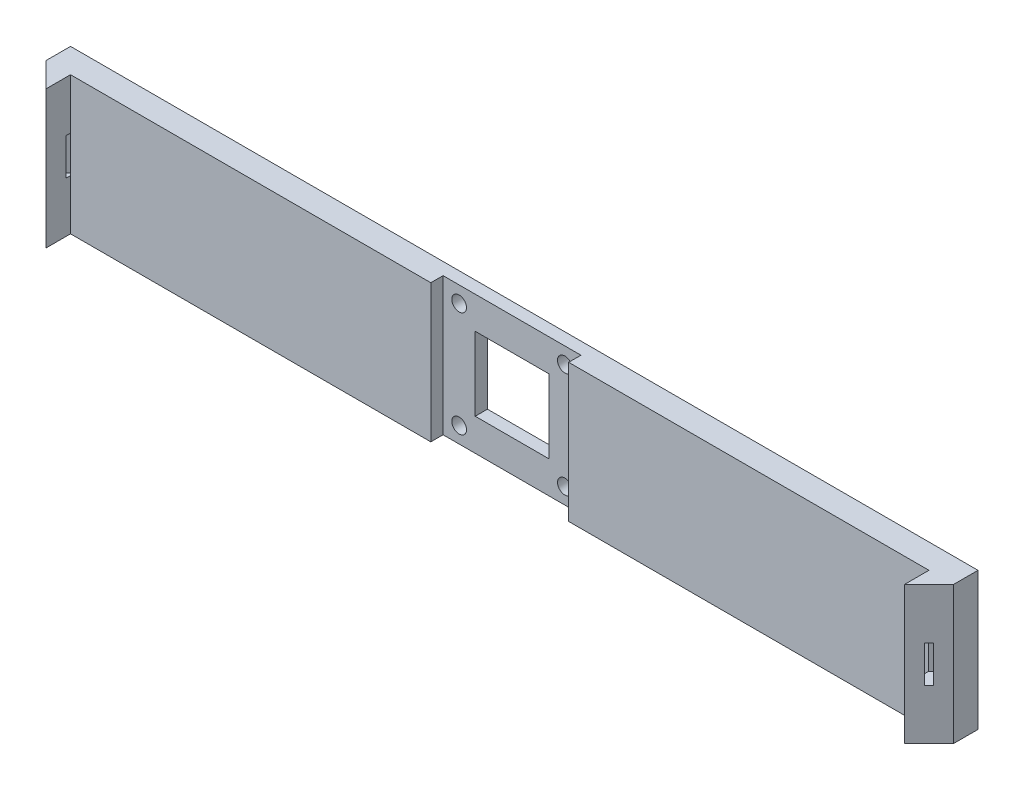
SolidWorks part; units mm, degrees
ref_plane "Front Plane" through (0, 0, 0) normal (0, 0, 1) x (1, 0, 0)
ref_plane "Top Plane" through (0, 0, 0) normal (0, 1, 0) x (1, 0, 0)
ref_plane "Right Plane" through (0, 0, 0) normal (1, 0, 0) x (0, 0, -1)
sketch "Sketch1" plane through (0, 0, 0) normal (0, 0, 1) x (1, 0, 0)
  line L1 (-175, -28.1) -> (175, -28.1)
  line L2 (-175, -28.1) -> (-175, 28.1)
  line L3 (-175, 28.1) -> (175, 28.1)
  line L4 (175, -28.1) -> (175, 28.1)
  line L5 (-175, -28.1) -> (175, 28.1) construction
  line L6 (-175, 28.1) -> (175, -28.1) construction
  point P0 (0, 0)
extrude "Boss-Extrude1" add sketch "Sketch1" along normal blind 10
sketch "Sketch2" plane through (0, 0, 10) normal (0, 0, 1) x (1, 0, 0)
  line L2 (175, 28.1) -> (-175, 28.1) construction
  line L3 (-28.1, -28.1) -> (28.1, -28.1)
  line L4 (-28.1, -28.1) -> (-28.1, 28.1)
  line L5 (-28.1, 28.1) -> (28.1, 28.1)
  line L6 (28.1, -28.1) -> (28.1, 28.1)
  point P8 (0, 0)
extrude "Cut-Extrude1" cut sketch "Sketch2" against normal blind 5
sketch "Sketch3" plane through (175, 0, 0) normal (1, 0, 0) x (0, 0, -1)
  line L1 (-10, 28.1) -> (0, 28.1)
  line L2 (-10, 28.1) -> (-10, -28.1)
  line L3 (-10, -28.1) -> (0, -28.1)
  line L4 (0, 28.1) -> (0, -28.1)
extrude "Boss-Extrude2" add sketch "Sketch3" along normal blind 10
sketch "Sketch4" plane through (0, 0, 10) normal (0, 0, 1) x (1, 0, 0)
  line L0 (28.1, -28.1) -> (185, -28.1) construction
  line L1 (185, 28.1) -> (175, 28.1)
  line L2 (185, 28.1) -> (185, -28.1)
  line L3 (185, -28.1) -> (175, -28.1)
  line L4 (175, 28.1) -> (175, -28.1)
extrude "Boss-Extrude3" add sketch "Sketch4" along normal blind 10
sketch "Sketch5" plane through (0, 28.1, 0) normal (0, 1, 0) x (1, 0, 0)
  line L0 (175, -20) -> (185, -10)
  line L1 (185, 0) -> (185, -20) construction
  line L2 (185, -10) -> (185, -20)
  line L3 (185, -20) -> (175, -20)
extrude "Cut-Extrude2" cut sketch "Sketch5" against normal blind 56.2
sketch "Sketch6" plane through (-175, 0, 0) normal (-1, 0, 0) x (0, 0, 1)
  line L1 (0, -28.1) -> (10, -28.1)
  line L2 (0, -28.1) -> (0, 28.1)
  line L3 (0, 28.1) -> (10, 28.1)
  line L4 (10, -28.1) -> (10, 28.1)
extrude "Boss-Extrude4" add sketch "Sketch6" along normal blind 10
sketch "Sketch7" plane through (0, 0, 10) normal (0, 0, 1) x (1, 0, 0)
  line L0 (-28.1, 28.1) -> (-185, 28.1) construction
  line L1 (-185, -28.1) -> (-175, -28.1)
  line L2 (-185, -28.1) -> (-185, 28.1)
  line L3 (-185, 28.1) -> (-175, 28.1)
  line L4 (-175, -28.1) -> (-175, 28.1)
extrude "Boss-Extrude5" add sketch "Sketch7" along normal blind 10
sketch "Sketch8" plane through (0, 28.1, 0) normal (0, 1, 0) x (1, 0, 0)
  line L0 (-175, -20) -> (-185, -10)
  line L1 (-185, -20) -> (-185, 0) construction
  line L2 (-185, -10) -> (-185, -20)
  line L3 (-185, -20) -> (-175, -20)
extrude "Cut-Extrude3" cut sketch "Sketch8" against normal blind 56.2
sketch "Sketch9" plane through (0, 0, 5) normal (0, 0, 1) x (1, 0, 0)
  line L3 (-15, -15) -> (15, -15)
  line L4 (-15, -15) -> (-15, 15)
  line L5 (-15, 15) -> (15, 15)
  line L6 (15, -15) -> (15, 15)
  point P4 (0, 0)
extrude "Cut-Extrude4" cut sketch "Sketch9" against normal blind 5
sketch "Sketch10" plane through (0, 0, 5) normal (0, 0, 1) x (1, 0, 0)
  circle A2 centre (21.55, 21.55) radius 3
  circle A3 centre (-21.55, -21.55) radius 3
  circle A4 centre (-21.55, 21.55) radius 3
  circle A5 centre (21.55, -21.55) radius 3
extrude "Cut-Extrude5" cut sketch "Sketch10" against normal blind 5
sketch "Sketch11" plane through (97.5, 0, 97.5) normal (0.7071, 0, 0.7071) x (0.7071, 0, -0.7071)
  line L3 (117.9226, -7.5) -> (115.4226, -7.5)
  line L4 (117.9226, -7.5) -> (117.9226, 7.5)
  line L5 (117.9226, 7.5) -> (115.4226, 7.5)
  line L6 (115.4226, -7.5) -> (115.4226, 7.5)
  line L7 (117.9226, -7.5) -> (115.4226, 7.5) construction
  line L8 (117.9226, 7.5) -> (115.4226, -7.5) construction
  point P6 (116.6726, 0)
  point P14 (116.6726, 0)
extrude "Cut-Extrude6" cut sketch "Sketch11" against normal blind 7
sketch "Sketch12" plane through (-97.5, 0, 97.5) normal (-0.7071, 0, 0.7071) x (0.7071, 0, 0.7071)
  line L2 (-117.9226, 7.5) -> (-115.4226, 7.5)
  line L3 (-117.9226, 7.5) -> (-117.9226, -7.5)
  line L4 (-117.9226, -7.5) -> (-115.4226, -7.5)
  line L5 (-115.4226, 7.5) -> (-115.4226, -7.5)
  line L6 (-117.9226, 7.5) -> (-115.4226, -7.5) construction
  line L7 (-117.9226, -7.5) -> (-115.4226, 7.5) construction
  point P4 (-116.6726, 0)
extrude "Cut-Extrude7" cut sketch "Sketch12" against normal blind 7
